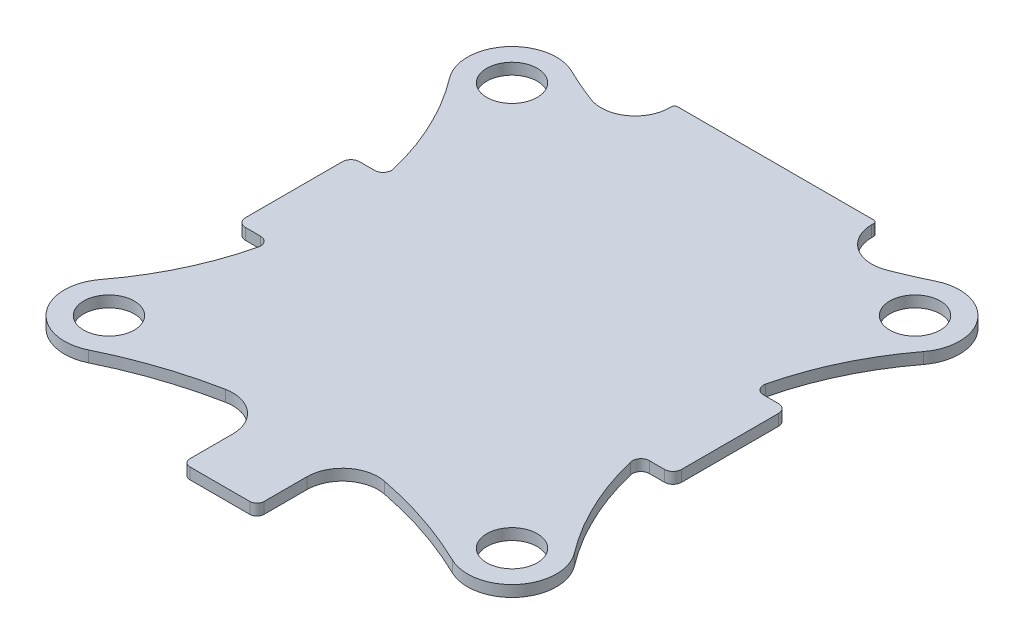
SolidWorks part; units mm, degrees
ref_plane "Front Plane" through (0, 0, 0) normal (0, 0, 1) x (1, 0, 0)
ref_plane "Top Plane" through (0, 0, 0) normal (0, 1, 0) x (1, 0, 0)
ref_plane "Right Plane" through (0, 0, 0) normal (1, 0, 0) x (0, 0, -1)
sketch "Sketch1" plane through (0, 0, 0) normal (0, 1, 0) x (1, 0, 0)
  line L0 (-17.9605, 17.9605) -> (17.9605, -17.9605) construction
  line L1 (-15.875, -17.78) -> (15.875, -17.78) construction
  line L2 (-15.875, -17.78) -> (-15.875, 17.78) construction
  line L3 (-15.875, 17.78) -> (15.875, 17.78) construction
  line L4 (15.875, -17.78) -> (15.875, 17.78) construction
  line L5 (-17.9605, -17.9605) -> (17.9605, 17.9605) construction
  line L6 (-20.7668, -15.1542) -> (-15.1542, -20.7668) construction
  line L7 (0, -17.78) -> (0, 17.78) construction
  line L8 (-15.875, 0) -> (15.875, 0) construction
  line L9 (20.7668, -15.1542) -> (15.1542, -20.7668) construction
  line L10 (-20.7668, 15.1542) -> (-15.1542, 20.7668) construction
  line L11 (20.7668, 15.1542) -> (15.1542, 20.7668) construction
  line L12 (-17.331, -5.08) -> (-18.669, -5.08)
  line L13 (-19.431, -4.318) -> (-19.431, 4.318)
  line L14 (-18.669, 5.08) -> (-17.331, 5.08)
  line L15 (18.669, 5.08) -> (17.331, 5.08)
  line L16 (19.431, -4.318) -> (19.431, 4.318)
  line L17 (-3.302, -21.5813) -> (-3.302, -25.4)
  line L18 (-2.667, -26.035) -> (2.667, -26.035)
  line L19 (3.302, -25.4) -> (3.302, -21.5813)
  line L20 (-9.017, 23.0455) -> (-9.017, 23.241)
  line L21 (-8.763, 23.495) -> (8.763, 23.495)
  line L22 (9.017, 23.241) -> (9.017, 23.0455)
  line L28 (17.331, -5.08) -> (18.669, -5.08)
  circle A0 centre (-17.9605, -17.9605) radius 3.9688 construction
  circle A1 centre (17.9605, -17.9605) radius 3.9688 construction
  circle A2 centre (17.9605, 17.9605) radius 3.9688 construction
  circle A3 centre (-17.9605, 17.9605) radius 3.9688 construction
  arc A4 (-21.1194, 15.5579) -> (-21.1194, -15.5579) centre (-41.5741, 0) cw construction
  arc A5 (-16.2197, 21.5271) -> (16.2197, 21.5271) centre (0, 54.7579) ccw construction
  arc A6 (-16.2197, -21.5271) -> (16.2197, -21.5271) centre (0, -54.7579) cw construction
  arc A7 (21.1194, 15.5579) -> (21.1194, -15.5579) centre (41.5741, 0) ccw construction
  arc A8 (-21.1194, 15.5579) -> (-16.2197, 21.5271) centre (-17.9605, 17.9605) cw
  arc A9 (16.2197, 21.5271) -> (21.1194, 15.5579) centre (17.9605, 17.9605) cw
  arc A10 (21.1194, -15.5579) -> (16.2197, -21.5271) centre (17.9605, -17.9605) cw
  arc A11 (-21.1194, -15.5579) -> (-16.2197, -21.5271) centre (-17.9605, -17.9605) ccw
  circle A12 centre (-17.9605, -17.9605) radius 2.25
  circle A13 centre (17.9605, -17.9605) radius 2.25
  circle A14 centre (17.9605, 17.9605) radius 2.25
  circle A15 centre (-17.9605, 17.9605) radius 2.25
  arc A16 (-21.1194, -15.5579) -> (-16.5902, -6.0205) centre (-41.5741, 0) ccw
  arc A17 (-17.331, -5.08) -> (-16.5902, -6.0205) centre (-17.331, -5.842) cw
  arc A18 (-21.1194, 15.5579) -> (-16.5902, 6.0205) centre (-41.5741, 0) cw
  arc A19 (-16.5902, 6.0205) -> (-17.331, 5.08) centre (-17.331, 5.842) cw
  arc A20 (-18.669, 5.08) -> (-19.431, 4.318) centre (-18.669, 4.318) ccw
  arc A21 (-19.431, -4.318) -> (-18.669, -5.08) centre (-18.669, -4.318) ccw
  arc A22 (16.5902, 6.0205) -> (17.331, 5.08) centre (17.331, 5.842) ccw
  arc A23 (21.1194, 15.5579) -> (16.5902, 6.0205) centre (41.5741, 0) ccw
  arc A24 (21.1194, -15.5579) -> (16.5902, -6.0205) centre (41.5741, 0) cw
  arc A25 (17.331, -5.08) -> (16.5902, -6.0205) centre (17.331, -5.842) ccw
  arc A26 (19.431, -4.318) -> (18.669, -5.08) centre (18.669, -4.318) cw
  arc A27 (18.669, 5.08) -> (19.431, 4.318) centre (18.669, 4.318) cw
  arc A28 (-16.2197, -21.5271) -> (-7.0854, -18.4652) centre (0, -54.7579) cw
  arc A29 (16.2197, -21.5271) -> (7.0854, -18.4652) centre (0, -54.7579) ccw
  arc A30 (-7.0854, -18.4652) -> (-3.302, -21.5813) centre (-6.477, -21.5813) cw
  arc A31 (7.0854, -18.4652) -> (3.302, -21.5813) centre (6.477, -21.5813) ccw
  arc A32 (-3.302, -25.4) -> (-2.667, -26.035) centre (-2.667, -25.4) ccw
  arc A33 (3.302, -25.4) -> (2.667, -26.035) centre (2.667, -25.4) cw
  arc A34 (-16.2197, 21.5271) -> (-13.1488, 20.1967) centre (0, 54.7579) ccw
  arc A35 (16.2197, 21.5271) -> (13.1488, 20.1967) centre (0, 54.7579) cw
  arc A36 (-9.017, 23.0455) -> (-13.1488, 20.1967) centre (-12.065, 23.0455) cw
  arc A37 (9.017, 23.0455) -> (13.1488, 20.1967) centre (12.065, 23.0455) ccw
  arc A38 (-8.763, 23.495) -> (-9.017, 23.241) centre (-8.763, 23.241) ccw
  arc A39 (8.763, 23.495) -> (9.017, 23.241) centre (8.763, 23.241) cw
  point P4 (0, 17.78)
  point P6 (15.875, 0)
  point P11 (0, 0)
  point P12 (0, 0)
  point P19 (-17.9605, -17.9605)
  point P60 (-19.431, 5.08)
  point P63 (-19.431, -5.08)
  point P72 (19.431, -5.08)
  point P73 (19.431, 5.08)
  point P82 (3.302, -17.9277)
  point P85 (-3.302, -26.035)
  point P88 (3.302, -26.035)
  point P95 (-9.017, 18.8962)
  point P98 (9.017, 18.8962)
  point P102 (-9.017, 23.495)
  point P105 (9.017, 23.495)
  dimension "D3" = 7.9375
  dimension "D8" = 0.762
  dimension "D9" = 0.762
  dimension "D10" = 0.762
  dimension "D11" = 0.762
  dimension "D14" = 3.175
  dimension "D15" = 3.175
  dimension "D16" = 0.635
  dimension "D17" = 0.635
  dimension "D20" = 3.048
  dimension "D21" = 3.048
  dimension "D22" = 4.5
  dimension "D23" = 0.254
  dimension "D24" = 0.254
  dimension "D1" = 31.75
  dimension "D2" = 35.56
  dimension "D4" = 50.8
  dimension "D5" = 3.556
  dimension "D6" = 5.08
  dimension "D7" = 5.08
  dimension "D12" = 6.604
  dimension "D13" = 8.255
  dimension "D18" = 5.715
  dimension "D19" = 18.034
extrude "Boss-Extrude2" add sketch "Sketch1" along normal blind 1 contours A12 | A13 | A14 | A15 | A28 A30 L17 A32 L18 A33 L19 A31 A29 A10 A24 A25 L28 A26 L16 A27 L15 A22 A23 A9 A35 A37 L22 A39 L21 A38 L20 A36 A34 A8 A18 A19 L14 A20 L13 A21 L12 A17 A16 A11 region at (-17.9605, 0, 17.9605) region at (17.9605, 0, 17.9605) region at (17.9605, 0, -17.9605) region at (-17.9605, 0, -17.9605)
